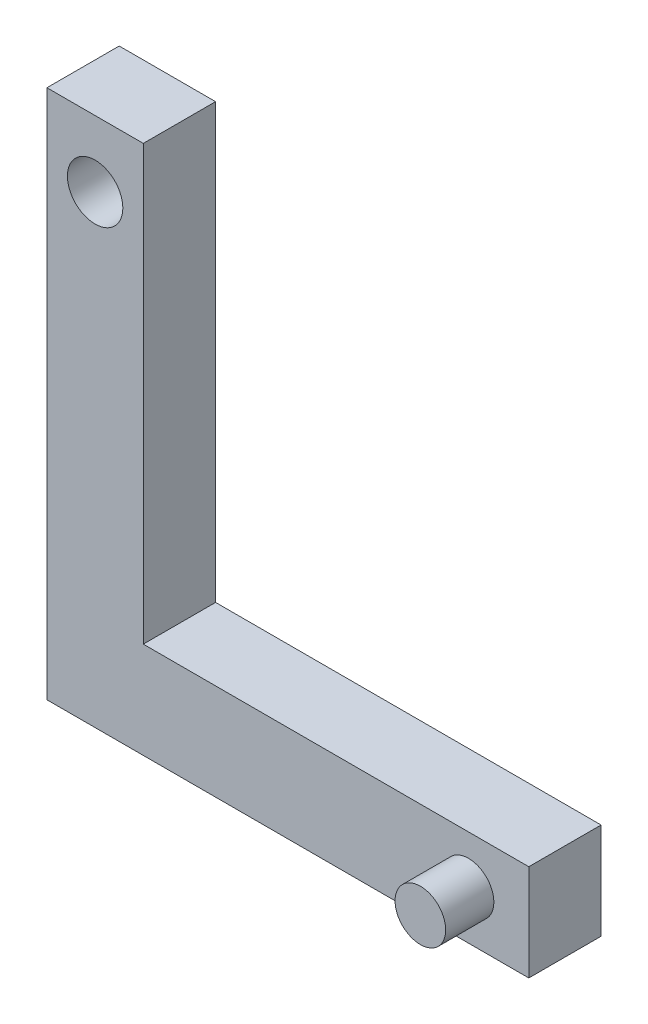
SolidWorks part; units mm, degrees
ref_plane "Alzado" through (0, 0, 0) normal (0, 0, 1) x (1, 0, 0)
ref_plane "Planta" through (0, 0, 0) normal (0, 1, 0) x (1, 0, 0)
ref_plane "Vista lateral" through (0, 0, 0) normal (1, 0, 0) x (0, 0, -1)
sketch "Croquis1" plane through (0, 0, 0) normal (0, 0, 1) x (1, 0, 0)
  line L1 (0, 0) -> (20, 0)
  line L2 (0, 0) -> (0, -4)
  line L3 (0, -4) -> (20, -4)
  line L4 (20, 0) -> (20, -4)
  circle A0 centre (0, -2.5) radius 1
  dimension "D5" = 2
  dimension "D1" = 4
  dimension "D2" = 20
  dimension "D3" = 20
  dimension "D4" = 2.5
extrude "Saliente-Extruir1" add sketch "Croquis1" along normal blind 3 contours L1 L4 L3 L2
sketch "Croquis3" plane through (0, 0, 0) normal (0, 0, -1) x (-1, 0, 0)
  line L0 (0, 0) -> (0, -4) construction
  line L1 (0, 0) -> (-20, 0) construction
  circle A0 centre (-17.5, -2) radius 1.05
  dimension "D3" = 2.1
  dimension "D1" = 17.5
  dimension "D2" = 2
sketch "Croquis4" plane through (0, 0, 0) normal (0, 0, -1) x (-1, 0, 0)
  line L0 (0, 0) -> (-20, 0) construction
  circle A0 centre (-2, -2) radius 1
  dimension "D2" = 2
  dimension "D3" = 2
sketch "Croquis5" plane through (0, 0, 3) normal (0, 0, 1) x (1, 0, 0)
  line L1 (0, 0) -> (4, 0)
  line L2 (0, 0) -> (0, 18)
  line L3 (0, 18) -> (4, 18)
  line L4 (4, 0) -> (4, 18)
  circle A0 centre (2, 15.25) radius 1.15
  circle A1 centre (2, -2) radius 1 construction
  line M9 (20, 0) -> (0, 0)
  dimension "D3" = 2.3
  dimension "D5" = 17.25
  dimension "D1" = 4
  dimension "D2" = 18
  dimension "D4" = 2
extrude "Saliente-Extruir2" add sketch "Croquis5" against normal blind 3 contours A0 | L4 L3 L2 A0 M9 region at (2, 8.6173, 3) region at (2, 15.25, 3)
extrude "Cortar-Extruir3" cut sketch "Croquis5<5>" against normal through all contours A0 region at (2, 15.25, 3)
sketch "Croquis5<5>" plane through (0, 0, 3) normal (0, 0, 1) x (1, 0, 0) same geometry as "Croquis5"
extrude "Saliente-Extruir4" add sketch "Croquis3" against normal blind 5
